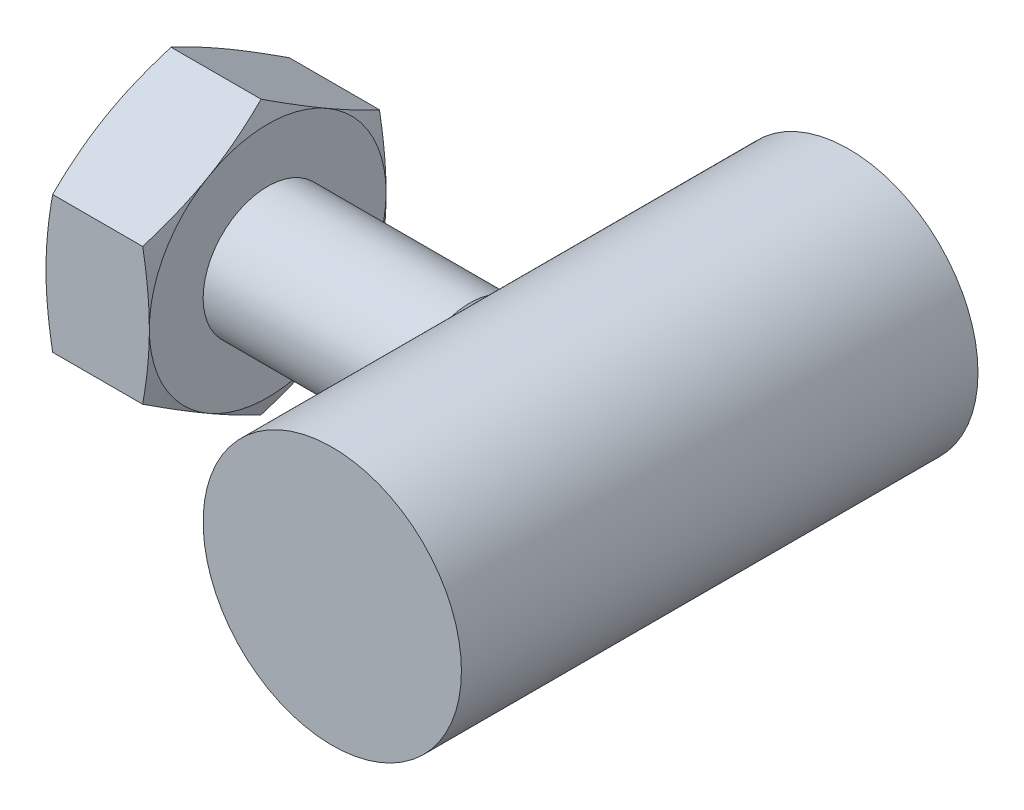
SolidWorks part; units mm, degrees
ref_plane "Front Plane" through (0, 0, 0) normal (0, 0, 1) x (1, 0, 0)
ref_plane "Top Plane" through (0, 0, 0) normal (0, 1, 0) x (1, 0, 0)
ref_plane "Right Plane" through (0, 0, 0) normal (1, 0, 0) x (0, 0, -1)
ref_plane "Plane1" through (0, 0, 0) normal (1, 0, 0) x (0, 0, -1)
sketch "Sketch1" plane through (0, 0, 0) normal (1, 0, 0) x (0, 0, -1)
  line L0 (-6, 0) -> (-6, 3)
  line L1 (-6, 3) -> (6, 3)
  line L2 (6, 3) -> (6, 0)
  line L3 (6, 0) -> (-6, 0)
  line L4 (6, 0) -> (-6, 0) construction
revolve "Revolve1" add sketch "Sketch1" angle 360 about L4 reverse direction yes
ref_plane "Plane2" through (0, 0, 0) normal (0, 0, 1) x (1, 0, 0)
sketch "Sketch2" plane through (0, 0, 0) normal (0, 0, 1) x (1, 0, 0)
  line L0 (-10, 0) -> (-10, 1.1935)
  line L1 (-10, 1.1935) -> (-9.6935, 1.5)
  line L2 (-9.6935, 1.5) -> (-2.8065, 1.5)
  line L3 (-2.8065, 1.5) -> (-2.5, 1.1935)
  line L4 (-2.5, 1.1935) -> (-2.5, 0)
  line L5 (-2.5, 0) -> (-10, 0)
  line L6 (-2.5, 0) -> (-10, 0) construction
revolve "Revolve2" add sketch "Sketch2" angle 360 about L6 reverse direction yes
cosmetic thread "Cosmetic Thread1" parameters "D1"=7.022, "D2"=2.387
ref_plane "Plane3" through (0, 0, 0) normal (0, 0, 1) x (1, 0, 0)
sketch "Sketch3" plane through (0, 0, 0) normal (0, 0, 1) x (1, 0, 0)
  line L0 (-9.9, 2.75) -> (-9.9, 1.5)
  line L1 (-9.9, 1.5) -> (-7.5, 1.5)
  line L2 (-7.5, 1.5) -> (-7.5, 2.75)
  line L3 (-7.5, 2.75) -> (-7.6548, 3.1754)
  line L4 (-7.6548, 3.1754) -> (-9.7452, 3.1754)
  line L5 (-9.7452, 3.1754) -> (-9.9, 2.75)
  line L6 (42.5, 0) -> (-57.5, 0) construction
revolve "Revolve3" add sketch "Sketch3" angle 360 about L6 reverse direction yes
ref_plane "Plane4" through (-7.5, 0, 0) normal (1, 0, 0) x (0, 0, -1)
sketch "Sketch4" plane through (-7.5, 0, 0) normal (1, 0, 0) x (0, 0, -1)
  line L0 (-5.5, -5.5) -> (5.5, -5.5)
  line L1 (5.5, -5.5) -> (5.5, 5.5)
  line L2 (5.5, 5.5) -> (-5.5, 5.5)
  line L3 (-5.5, 5.5) -> (-5.5, -5.5)
  line L4 (-2.75, -1.5877) -> (0, -3.1754)
  line L5 (0, -3.1754) -> (2.75, -1.5877)
  line L6 (2.75, -1.5877) -> (2.75, 1.5877)
  line L7 (2.75, 1.5877) -> (0, 3.1754)
  line L8 (0, 3.1754) -> (-2.75, 1.5877)
  line L9 (-2.75, 1.5877) -> (-2.75, -1.5877)
extrude "Cut-Extrude1" cut sketch "Sketch4" against normal blind 2.4
